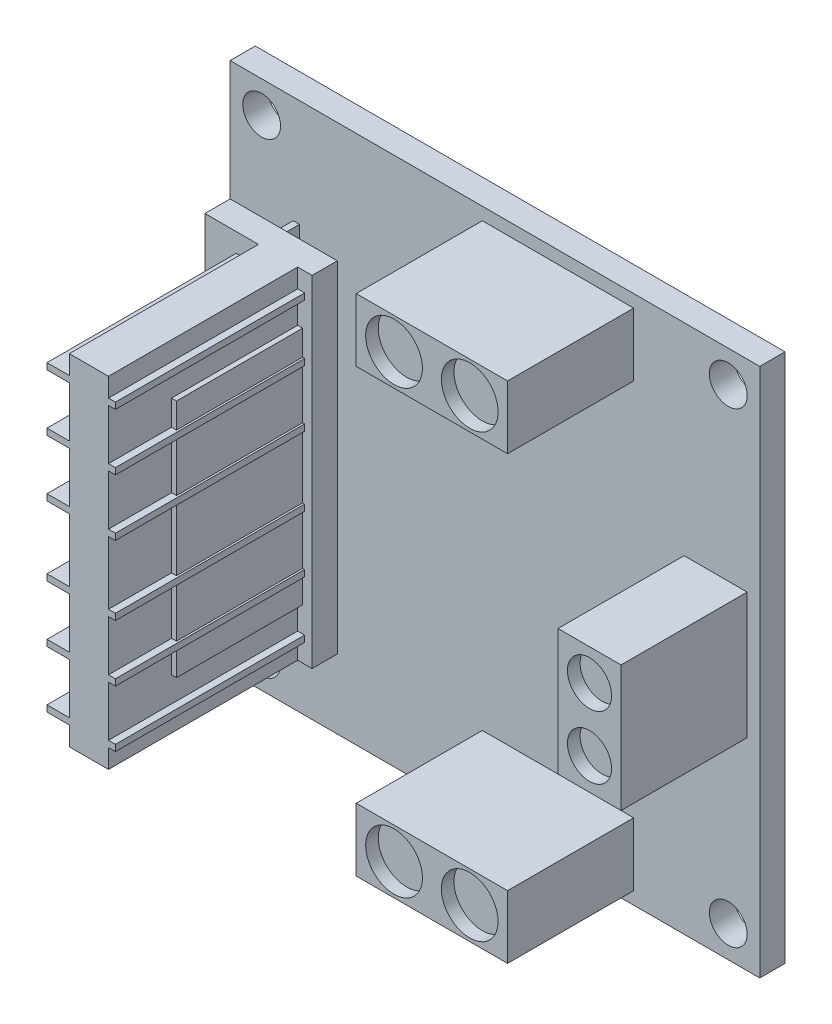
SolidWorks part; units mm, degrees
ref_plane "Front Plane" through (0, 0, 0) normal (0, 0, 1) x (1, 0, 0)
ref_plane "Top Plane" through (0, 0, 0) normal (0, 1, 0) x (1, 0, 0)
ref_plane "Right Plane" through (0, 0, 0) normal (1, 0, 0) x (0, 0, -1)
sketch "Sketch1" plane through (0, 0, 0) normal (0, 0, 1) x (1, 0, 0)
  line L0 (-20.2922, -148.6327) -> (-11.9422, -148.6327) construction
  line L1 (14.4712, -106.6327) -> (56.4712, -106.6327)
  line L2 (14.4712, -106.6327) -> (14.4712, -148.6327)
  line L3 (14.4712, -148.6327) -> (56.4712, -148.6327)
  line L4 (56.4712, -106.6327) -> (56.4712, -148.6327)
  dimension "D3" = 0
extrude "Boss-Extrude1" add sketch "Sketch1" along normal blind 2
sketch "Sketch2" plane through (0, 0, 2) normal (0, 0, 1) x (1, 0, 0)
  line L0 (14.4712, -127.6327) -> (56.4712, -127.6327) construction
  line L1 (19.4712, -115.1327) -> (19.9712, -115.1327)
  line L2 (19.4712, -115.1327) -> (19.4712, -140.1327)
  line L3 (19.4712, -140.1327) -> (19.9712, -140.1327)
  line L4 (19.9712, -115.1327) -> (19.9712, -140.1327)
  line L5 (14.4712, -106.6327) -> (14.4712, -148.6327) construction
  line L6 (56.4712, -148.6327) -> (56.4712, -106.6327) construction
  dimension "D1" = 0.5
  dimension "D2" = 25
  dimension "D3" = 12.5
  dimension "D4" = 5
extrude "Boss-Extrude2" add sketch "Sketch2" along normal blind 2
sketch "Sketch4" plane through (0, 0, 4) normal (0, 0, 1) x (1, 0, 0)
  line L0 (19.9712, -140.1327) -> (19.9712, -115.1327) construction
  line L1 (16.4712, -114.1327) -> (24.9712, -114.1327)
  line L2 (16.4712, -114.1327) -> (16.4712, -141.1327)
  line L3 (16.4712, -141.1327) -> (24.9712, -141.1327)
  line L4 (24.9712, -114.1327) -> (24.9712, -141.1327)
  line L5 (19.4712, -115.1327) -> (19.4712, -140.1327) construction
  line L6 (19.9712, -115.1327) -> (19.4712, -115.1327) construction
  line L7 (19.4712, -140.1327) -> (19.9712, -140.1327) construction
  dimension "D1" = 5
  dimension "D2" = 3
  dimension "D3" = 1
  dimension "D4" = 1
extrude "Boss-Extrude3" add sketch "Sketch4" along normal blind 2
sketch "Sketch5" plane through (0, 0, 6) normal (0, 0, 1) x (1, 0, 0)
  line L0 (16.4712, -127.6327) -> (24.9712, -127.6327) construction
  line L1 (18.9526, -115.6327) -> (24.3791, -115.6327)
  line L2 (18.9526, -115.6327) -> (18.9526, -116.1327)
  line L3 (18.9526, -116.1327) -> (24.3791, -116.1327)
  line L4 (24.3791, -115.6327) -> (24.3791, -116.1327)
  line L5 (18.9526, -120.1327) -> (24.3791, -120.1327)
  line L6 (18.9526, -120.1327) -> (18.9526, -120.6327)
  line L7 (18.9526, -120.6327) -> (24.3791, -120.6327)
  line L8 (24.3791, -120.1327) -> (24.3791, -120.6327)
  line L9 (18.9526, -124.6327) -> (24.3791, -124.6327)
  line L10 (18.9526, -124.6327) -> (18.9526, -125.1327)
  line L11 (18.9526, -125.1327) -> (24.3791, -125.1327)
  line L12 (24.3791, -124.6327) -> (24.3791, -125.1327)
  line L13 (16.4712, -114.1327) -> (16.4712, -141.1327) construction
  line L14 (24.9712, -141.1327) -> (24.9712, -114.1327) construction
  line L15 (24.3791, -130.6327) -> (24.3791, -130.1327)
  line L16 (18.9526, -130.1327) -> (24.3791, -130.1327)
  line L17 (18.9526, -130.6327) -> (18.9526, -130.1327)
  line L18 (18.9526, -130.6327) -> (24.3791, -130.6327)
  line L19 (24.3791, -135.1327) -> (24.3791, -134.6327)
  line L20 (18.9526, -134.6327) -> (24.3791, -134.6327)
  line L21 (18.9526, -135.1327) -> (18.9526, -134.6327)
  line L22 (18.9526, -135.1327) -> (24.3791, -135.1327)
  line L23 (24.3791, -139.6327) -> (24.3791, -139.1327)
  line L24 (18.9526, -139.1327) -> (24.3791, -139.1327)
  line L25 (18.9526, -139.6327) -> (18.9526, -139.1327)
  line L26 (18.9526, -139.6327) -> (24.3791, -139.6327)
  dimension "D1" = 0.5
  dimension "D2" = 0.5
  dimension "D3" = 0.5
  dimension "D4" = 2.5
  dimension "D5" = 4
  dimension "D6" = 4
extrude "Boss-Extrude4" add sketch "Sketch5" along normal blind 15
sketch "Sketch6" plane through (0, 0, 6) normal (0, 0, 1) x (1, 0, 0)
  line L0 (24.9712, -114.1327) -> (16.4712, -114.1327) construction
  line L1 (23.8288, -114.1327) -> (20.7212, -114.1327)
  line L2 (23.8288, -114.1327) -> (23.8288, -141.1327)
  line L3 (23.8288, -141.1327) -> (20.7212, -141.1327)
  line L4 (20.7212, -114.1327) -> (20.7212, -141.1327)
  line L5 (16.4712, -141.1327) -> (24.9712, -141.1327) construction
extrude "Boss-Extrude5" add sketch "Sketch6" along normal up to surface (15 mm away) up to face at (21.6658, -115.8827, 21)
sketch "Sketch7" plane through (0, 0, 6) normal (0, 0, 1) x (1, 0, 0)
  line L1 (21.7212, -118.1327) -> (24.2212, -118.1327)
  line L2 (21.7212, -118.1327) -> (21.7212, -137.1327)
  line L3 (21.7212, -137.1327) -> (24.2212, -137.1327)
  line L4 (24.2212, -118.1327) -> (24.2212, -137.1327)
  line L5 (18.9526, -116.1327) -> (20.7212, -116.1327) construction
  line L6 (20.7212, -139.1327) -> (18.9526, -139.1327) construction
  line L7 (20.7212, -141.1327) -> (20.7212, -114.1327) construction
  dimension "D1" = 2.5
  dimension "D2" = 2
  dimension "D3" = 2
  dimension "D4" = 1
extrude "Boss-Extrude6" add sketch "Sketch7" along normal blind 10
sketch "Sketch8" plane through (0, 0, 2) normal (0, 0, 1) x (1, 0, 0)
  line L0 (56.4712, -148.6327) -> (56.4712, -106.6327) construction
  line L1 (34.4712, -107.6327) -> (46.4712, -107.6327)
  line L2 (34.4712, -107.6327) -> (34.4712, -112.6327)
  line L3 (34.4712, -112.6327) -> (46.4712, -112.6327)
  line L4 (46.4712, -107.6327) -> (46.4712, -112.6327)
  line L5 (34.4712, -142.6327) -> (46.4712, -142.6327)
  line L6 (34.4712, -142.6327) -> (34.4712, -147.6327)
  line L7 (34.4712, -147.6327) -> (46.4712, -147.6327)
  line L8 (46.4712, -142.6327) -> (46.4712, -147.6327)
  line L9 (50.4712, -122.6327) -> (55.4712, -122.6327)
  line L10 (50.4712, -122.6327) -> (50.4712, -132.6327)
  line L11 (50.4712, -132.6327) -> (55.4712, -132.6327)
  line L12 (55.4712, -122.6327) -> (55.4712, -132.6327)
  line L13 (14.4712, -127.6327) -> (56.4712, -127.6327) construction
  line L14 (14.4712, -106.6327) -> (14.4712, -148.6327) construction
  line L15 (56.4712, -106.6327) -> (14.4712, -106.6327) construction
  line L16 (14.4712, -148.6327) -> (56.4712, -148.6327) construction
  dimension "D1" = 5
  dimension "D2" = 1
  dimension "D3" = 5
  dimension "D4" = 10
  dimension "D5" = 12
  dimension "D6" = 10
  dimension "D7" = 10
  dimension "D8" = 12
  dimension "D9" = 5
  dimension "D10" = 5
  dimension "D11" = 1
  dimension "D12" = 1
extrude "Boss-Extrude7" add sketch "Sketch8" along normal blind 10
sketch "Sketch9" plane through (0, 0, 12) normal (0, 0, 1) x (1, 0, 0)
  line L0 (34.4712, -107.6327) -> (34.4712, -112.6327) construction
  line L1 (46.4712, -112.6327) -> (46.4712, -107.6327) construction
  line L2 (55.4712, -122.6327) -> (50.4712, -122.6327) construction
  line L3 (14.4712, -127.6327) -> (56.4712, -127.6327) construction
  line L4 (14.4712, -106.6327) -> (14.4712, -148.6327) construction
  line L5 (56.4712, -148.6327) -> (56.4712, -106.6327) construction
  circle A0 centre (37.4712, -110.1327) radius 2.25
  circle A1 centre (43.4712, -110.1327) radius 2.25
  circle A2 centre (52.9712, -125.1327) radius 1.75
  circle A3 centre (52.9712, -130.1327) radius 1.75
  circle A4 centre (43.4712, -145.1327) radius 2.25
  circle A5 centre (37.4712, -145.1327) radius 2.25
  dimension "D1" = 4.5
  dimension "D2" = 4.5
  dimension "D3" = 3
  dimension "D4" = 3
  dimension "D5" = 3.5
  dimension "D6" = 2.5
extrude "Cut-Extrude1" cut sketch "Sketch9" against normal blind 1
sketch "Sketch10" plane through (0, 0, 2) normal (0, 0, 1) x (1, 0, 0)
  line L0 (56.4712, -127.6327) -> (14.4712, -127.6327) construction
  line L1 (56.4712, -148.6327) -> (56.4712, -106.6327) construction
  line L2 (14.4712, -106.6327) -> (14.4712, -148.6327) construction
  line L3 (35.4712, -106.6327) -> (35.4712, -148.6327) construction
  line L4 (56.4712, -106.6327) -> (14.4712, -106.6327) construction
  line L5 (14.4712, -148.6327) -> (56.4712, -148.6327) construction
  circle A0 centre (53.9712, -109.1327) radius 1.5
  circle A1 centre (16.9712, -109.1327) radius 1.5
  circle A2 centre (16.9712, -146.1327) radius 1.5
  circle A3 centre (53.9712, -146.1327) radius 1.5
extrude "Cut-Extrude2" cut sketch "Sketch10" against normal through all
